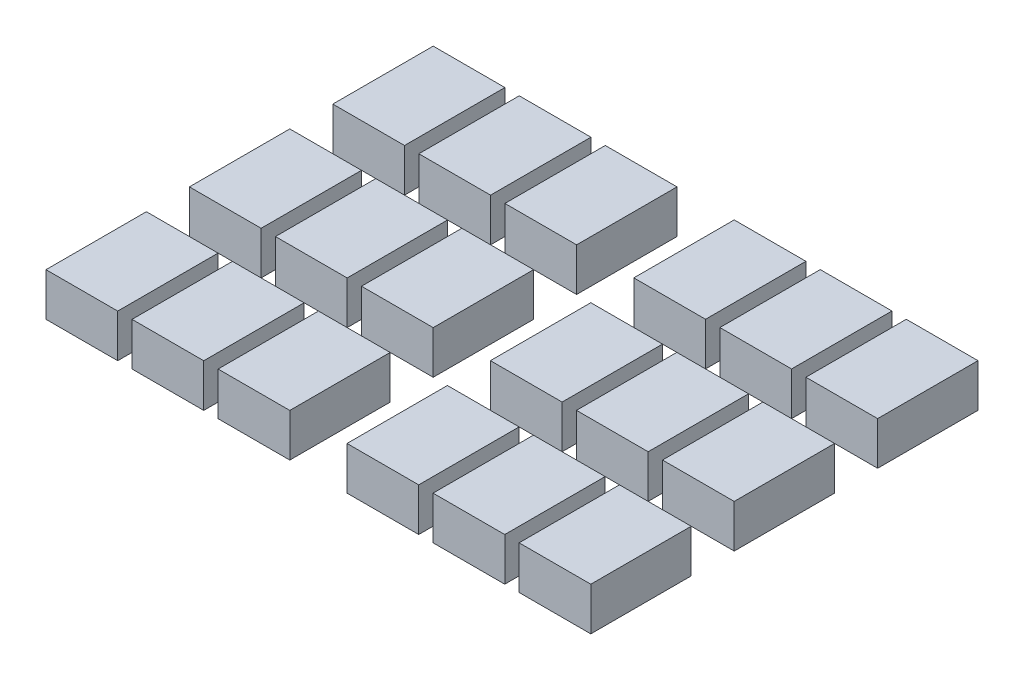
SolidWorks part; units mm, degrees
ref_plane "Front Plane" through (0, 0, 0) normal (0, 0, 1) x (1, 0, 0)
ref_plane "Top Plane" through (0, 0, 0) normal (0, 1, 0) x (1, 0, 0)
ref_plane "Right Plane" through (0, 0, 0) normal (1, 0, 0) x (0, 0, -1)
sketch "First Class Seat" plane through (0, 0, 0) normal (0, 1, 0) x (1, 0, 0)
  line L0 (-1320.292, 13858.7872) -> (-812.292, 13858.7872)
  line L1 (-1993.392, 18288) -> (1993.392, 18288) construction
  line L2 (-1993.392, 18288) -> (-1993.392, -18288) construction
  line L3 (-1993.392, -18288) -> (1993.392, -18288) construction
  line L4 (1993.392, 18288) -> (1993.392, -18288) construction
  line L5 (-1993.392, 18288) -> (1993.392, -18288) construction
  line L6 (-1993.392, -18288) -> (1993.392, 18288) construction
  line L11 (-1929.892, 13858.7872) -> (-1421.892, 13858.7872)
  line L12 (-1929.892, 13858.7872) -> (-1929.892, 13147.5872)
  line L13 (-1929.892, 13147.5872) -> (-1421.892, 13147.5872)
  line L14 (-1421.892, 13858.7872) -> (-1421.892, 13147.5872)
  line L15 (-1320.292, 13858.7872) -> (-1320.292, 13147.5872)
  line L16 (-1320.292, 13147.5872) -> (-812.292, 13147.5872)
  line L17 (-812.292, 13858.7872) -> (-812.292, 13147.5872)
  line L18 (-710.692, 13858.7872) -> (-202.692, 13858.7872)
  line L19 (-710.692, 13858.7872) -> (-710.692, 13147.5872)
  line L20 (-710.692, 13147.5872) -> (-202.692, 13147.5872)
  line L21 (-202.692, 13858.7872) -> (-202.692, 13147.5872)
  line L22 (-1320.292, 14874.7872) -> (-812.292, 14874.7872)
  line L23 (-1320.292, 14874.7872) -> (-1320.292, 14163.5872)
  line L24 (-1320.292, 14163.5872) -> (-812.292, 14163.5872)
  line L25 (-812.292, 14874.7872) -> (-812.292, 14163.5872)
  line L26 (-710.692, 14874.7872) -> (-202.692, 14874.7872)
  line L27 (-710.692, 14874.7872) -> (-710.692, 14163.5872)
  line L28 (-710.692, 14163.5872) -> (-202.692, 14163.5872)
  line L29 (-202.692, 14874.7872) -> (-202.692, 14163.5872)
  line L30 (-1320.292, 15890.7872) -> (-812.292, 15890.7872)
  line L31 (-1320.292, 15890.7872) -> (-1320.292, 15179.5872)
  line L32 (-1320.292, 15179.5872) -> (-812.292, 15179.5872)
  line L33 (-812.292, 15890.7872) -> (-812.292, 15179.5872)
  line L34 (-710.692, 15890.7872) -> (-202.692, 15890.7872)
  line L35 (-710.692, 15890.7872) -> (-710.692, 15179.5872)
  line L36 (-710.692, 15179.5872) -> (-202.692, 15179.5872)
  line L37 (-202.692, 15890.7872) -> (-202.692, 15179.5872)
  line L38 (-1929.892, 14874.7872) -> (-1421.892, 14874.7872)
  line L39 (-1929.892, 14874.7872) -> (-1929.892, 14163.5872)
  line L40 (-1929.892, 14163.5872) -> (-1421.892, 14163.5872)
  line L41 (-1421.892, 14874.7872) -> (-1421.892, 14163.5872)
  line L42 (-1929.892, 15890.7872) -> (-1421.892, 15890.7872)
  line L43 (-1929.892, 15890.7872) -> (-1929.892, 15179.5872)
  line L44 (-1929.892, 15179.5872) -> (-1421.892, 15179.5872)
  line L45 (-1421.892, 15890.7872) -> (-1421.892, 15179.5872)
  line L46 (0, 18288) -> (0, -18288) construction
  line L47 (1421.892, 15890.7872) -> (1421.892, 15179.5872)
  line L48 (1929.892, 15179.5872) -> (1421.892, 15179.5872)
  line L49 (1929.892, 15890.7872) -> (1929.892, 15179.5872)
  line L50 (1929.892, 15890.7872) -> (1421.892, 15890.7872)
  line L51 (1421.892, 14874.7872) -> (1421.892, 14163.5872)
  line L52 (1929.892, 14163.5872) -> (1421.892, 14163.5872)
  line L53 (1929.892, 14874.7872) -> (1929.892, 14163.5872)
  line L54 (1929.892, 14874.7872) -> (1421.892, 14874.7872)
  line L55 (202.692, 15890.7872) -> (202.692, 15179.5872)
  line L56 (710.692, 15179.5872) -> (202.692, 15179.5872)
  line L57 (710.692, 15890.7872) -> (710.692, 15179.5872)
  line L58 (710.692, 15890.7872) -> (202.692, 15890.7872)
  line L59 (812.292, 15890.7872) -> (812.292, 15179.5872)
  line L60 (1320.292, 15179.5872) -> (812.292, 15179.5872)
  line L61 (1320.292, 15890.7872) -> (1320.292, 15179.5872)
  line L62 (1320.292, 15890.7872) -> (812.292, 15890.7872)
  line L63 (202.692, 14874.7872) -> (202.692, 14163.5872)
  line L64 (710.692, 14163.5872) -> (202.692, 14163.5872)
  line L65 (710.692, 14874.7872) -> (710.692, 14163.5872)
  line L66 (710.692, 14874.7872) -> (202.692, 14874.7872)
  line L67 (812.292, 14874.7872) -> (812.292, 14163.5872)
  line L68 (1320.292, 14163.5872) -> (812.292, 14163.5872)
  line L69 (1320.292, 14874.7872) -> (1320.292, 14163.5872)
  line L70 (1320.292, 14874.7872) -> (812.292, 14874.7872)
  line L71 (202.692, 13858.7872) -> (202.692, 13147.5872)
  line L72 (710.692, 13147.5872) -> (202.692, 13147.5872)
  line L73 (710.692, 13858.7872) -> (710.692, 13147.5872)
  line L74 (710.692, 13858.7872) -> (202.692, 13858.7872)
  line L75 (812.292, 13858.7872) -> (812.292, 13147.5872)
  line L76 (1320.292, 13147.5872) -> (812.292, 13147.5872)
  line L77 (1320.292, 13858.7872) -> (1320.292, 13147.5872)
  line L78 (1421.892, 13858.7872) -> (1421.892, 13147.5872)
  line L79 (1929.892, 13147.5872) -> (1421.892, 13147.5872)
  line L80 (1929.892, 13858.7872) -> (1929.892, 13147.5872)
  line L81 (1929.892, 13858.7872) -> (1421.892, 13858.7872)
  line L82 (1320.292, 13858.7872) -> (812.292, 13858.7872)
  point P0 (0, 0)
  point P10 (-1874.4664, 14436.0926)
  point P45 (0, 0)
  point P46 (0, 0)
  point P47 (-1893.0211, 14361.6296)
  point P84 (-1942.592, 14425.8266)
  point P85 (-1929.892, 12907.0433)
  point P86 (-1929.892, 13226.5881)
  point P87 (-1929.892, 13139.258)
  point P88 (-1929.892, 16238.2689)
  point P89 (0, 0)
  point P90 (-1993.392, 11778.9178)
  point P91 (0, 0)
  point P92 (-1929.892, 12245.8872)
  dimension "D1" = 36576
  dimension "D2" = 3986.784
  dimension "D3" = 508
  dimension "D4" = 711.2
  dimension "D7" = 1016
  dimension "D8" = 101.6
  dimension "D9" = 63.5
  dimension "D10" = 405.384
  dimension "D5" = 3
  dimension "D6" = 3
extrude "First Class Seat-" add sketch "First Class Seat" along normal blind 304.8
sketch "First Class LAV" plane through (0, 0, 0) normal (0, 1, 0) x (1, 0, 0)
  line L1 (-1993.392, 18288) -> (-977.392, 18288)
  line L2 (-1993.392, 18288) -> (-1993.392, 17322.8)
  line L3 (-1993.392, 17322.8) -> (-977.392, 17322.8)
  line L4 (-977.392, 18288) -> (-977.392, 17322.8)
  line L5 (-1993.392, 18288) -> (-1993.392, -18288) construction
  line L6 (0, 0) -> (0, 585.7806) construction
  line L9 (-1993.392, 18288) -> (1993.392, -18288) construction
  line L10 (0, 18288) -> (0, -18288) construction
  line L11 (977.392, 18288) -> (977.392, 17322.8)
  line L12 (1993.392, 17322.8) -> (977.392, 17322.8)
  line L13 (1993.392, 18288) -> (1993.392, 17322.8)
  line L14 (1993.392, 18288) -> (977.392, 18288)
  point P16 (-1972.7451, 17206.2188)
  point P17 (-1993.392, 16421.1)
  dimension "D1" = 1016
  dimension "D2" = 965.2
sketch "First Class Galley" plane through (0, 0, 0) normal (0, 1, 0) x (1, 0, 0)
  line L0 (-1993.392, 18288) -> (-1993.392, -18288) construction
  line L1 (-1993.392, 16508.5663) -> (-1028.192, 16508.5663)
  line L2 (-1993.392, 16508.5663) -> (-1993.392, 16127.5663)
  line L3 (-1993.392, 16127.5663) -> (-1028.192, 16127.5663)
  line L4 (-1028.192, 16508.5663) -> (-1028.192, 16127.5663)
  line L5 (-1993.392, 16892.6143) -> (-1028.192, 16892.6143)
  line L6 (-1993.392, 16892.6143) -> (-1993.392, 16511.6143)
  line L7 (-1993.392, 16511.6143) -> (-1028.192, 16511.6143)
  line L8 (-1028.192, 16892.6143) -> (-1028.192, 16511.6143)
  line L9 (-1993.392, 17276.6623) -> (-1028.192, 17276.6623)
  line L10 (-1993.392, 17276.6623) -> (-1993.392, 16895.6623)
  line L11 (-1993.392, 16895.6623) -> (-1028.192, 16895.6623)
  line L12 (-1028.192, 17276.6623) -> (-1028.192, 16895.6623)
  line L13 (0, -20116.8) -> (0, 20116.8) construction
  line L14 (1028.192, 17276.6623) -> (1028.192, 16895.6623)
  line L15 (1993.392, 16895.6623) -> (1028.192, 16895.6623)
  line L16 (1993.392, 17276.6623) -> (1993.392, 16895.6623)
  line L17 (1993.392, 17276.6623) -> (1028.192, 17276.6623)
  line L18 (1028.192, 16892.6143) -> (1028.192, 16511.6143)
  line L19 (1993.392, 16511.6143) -> (1028.192, 16511.6143)
  line L20 (1993.392, 16892.6143) -> (1993.392, 16511.6143)
  line L21 (1993.392, 16892.6143) -> (1028.192, 16892.6143)
  line L22 (1028.192, 16508.5663) -> (1028.192, 16127.5663)
  line L23 (1993.392, 16127.5663) -> (1028.192, 16127.5663)
  line L24 (1993.392, 16508.5663) -> (1993.392, 16127.5663)
  line L25 (1993.392, 16508.5663) -> (1028.192, 16508.5663)
  point P4 (-1993.392, 14804.2428)
  point P5 (-1993.392, 15167.2745)
  point P30 (-1993.392, 16071.3168)
  dimension "D1" = 381
  dimension "D2" = 965.2
  dimension "D4" = 3.048
  dimension "D3" = 3
sketch "First Class Coat Room" plane through (0, 0, 0) normal (0, 1, 0) x (1, 0, 0)
  line L0 (-1993.392, 18288) -> (-1993.392, -18288) construction
  line L1 (-1993.392, 13011.8143) -> (1993.392, 13011.8143)
  line L2 (-1993.392, 13011.8143) -> (-1993.392, 12326.0143)
  line L3 (-1993.392, 12326.0143) -> (1993.392, 12326.0143)
  line L4 (1993.392, 13011.8143) -> (1993.392, 12326.0143)
  line L5 (1993.392, 18288) -> (1993.392, -18288) construction
  point P8 (-1993.392, 11424.9048)
  point P9 (-1993.392, 13011.8143)
  dimension "D1" = 685.8
sketch "EM Exits" plane through (0, 0, 0) normal (0, 1, 0) x (1, 0, 0)
  line L0 (-1993.392, 18288) -> (-1993.392, -18288) construction
  line L1 (-1993.392, 12326.0143) -> (-1940.4514, 12326.0143)
  line L2 (-1993.392, 12326.0143) -> (-1993.392, 11259.2143)
  line L3 (-1993.392, 11259.2143) -> (-1940.4514, 11259.2143)
  line L4 (-1940.4514, 12326.0143) -> (-1940.4514, 11259.2143)
  line L5 (-1993.392, 12326.0143) -> (1993.392, 12326.0143) construction
  line L6 (0, -20116.8) -> (0, 20116.8) construction
  line L7 (-1993.392, -7028.7857) -> (-1940.4514, -7028.7857)
  line L8 (-1993.392, -7028.7857) -> (-1993.392, -8095.5857)
  line L9 (-1993.392, -8095.5857) -> (-1940.4514, -8095.5857)
  line L10 (-1940.4514, -7028.7857) -> (-1940.4514, -8095.5857)
  line L11 (1940.4514, -7028.7857) -> (1940.4514, -8095.5857)
  line L12 (1993.392, -8095.5857) -> (1940.4514, -8095.5857)
  line L13 (1993.392, -7028.7857) -> (1993.392, -8095.5857)
  line L14 (1993.392, -7028.7857) -> (1940.4514, -7028.7857)
  line L15 (1940.4514, 12326.0143) -> (1940.4514, 11259.2143)
  line L16 (1993.392, 11259.2143) -> (1940.4514, 11259.2143)
  line L17 (1993.392, 12326.0143) -> (1993.392, 11259.2143)
  line L18 (1993.392, 12326.0143) -> (1940.4514, 12326.0143)
  line L19 (-1940.4514, 11259.2143) -> (1940.4514, 11259.2143) construction
  line L20 (-1940.4514, -7028.7857) -> (1940.4514, -7028.7857) construction
  line L21 (1940.4514, -8095.5857) -> (-1940.4514, -8095.5857) construction
  line L22 (-1940.4514, -7562.1857) -> (1940.4514, -7562.1857) construction
  line L23 (-1940.4514, 11792.6143) -> (1940.4514, 11792.6143) construction
  line L24 (1940.4514, 12326.0143) -> (-1940.4514, 12326.0143) construction
  point P26 (-1993.392, 12326.0143)
  dimension "D1" = 1066.8
  dimension "D2" = 0
  dimension "D3" = 1066.8
  dimension "D4" = 18288
sketch "Econ LAV" plane through (0, 0, 0) normal (0, 1, 0) x (1, 0, 0)
  line L0 (-1993.392, 11259.2143) -> (-977.392, 11259.2143)
  line L1 (-1993.392, 11259.2143) -> (-1993.392, 10294.0143)
  line L2 (-1993.392, 10294.0143) -> (-977.392, 10294.0143)
  line L3 (-977.392, 11259.2143) -> (-977.392, 10294.0143)
  line L8 (-1993.392, -17322.8) -> (-977.392, -17322.8)
  line L9 (-1993.392, -17322.8) -> (-1993.392, -18288)
  line L10 (-1993.392, -18288) -> (-977.392, -18288)
  line L11 (-977.392, -17322.8) -> (-977.392, -18288)
  line L12 (0, -20116.8) -> (0, 20116.8) construction
  line L13 (977.392, -17322.8) -> (977.392, -18288)
  line L14 (1993.392, -18288) -> (977.392, -18288)
  line L15 (1993.392, -17322.8) -> (1993.392, -18288)
  line L16 (1993.392, -17322.8) -> (977.392, -17322.8)
  line L17 (977.392, 11259.2143) -> (977.392, 10294.0143)
  line L18 (1993.392, 10294.0143) -> (977.392, 10294.0143)
  line L19 (1993.392, 11259.2143) -> (1993.392, 10294.0143)
  line L20 (1993.392, 11259.2143) -> (977.392, 11259.2143)
  point P4 (-1748.2194, 9202.9834)
  point P5 (-1772.2723, 9247.487)
  point P6 (-1993.392, 10358.1048)
  point P8 (-1786.9164, 7219.1182)
  point P13 (-1993.392, -17386.3)
  dimension "D1" = 1016
  dimension "D2" = 965.2
  dimension "D3" = 1016
  dimension "D4" = 965.2
sketch "Econ Seat" plane through (0, 0, 0) normal (0, 1, 0) x (1, 0, 0)
  line L1 (-1929.892, -16523.2246) -> (-1472.692, -16523.2246)
  line L2 (-1929.892, -16523.2246) -> (-1929.892, -17158.2246)
  line L3 (-1929.892, -17158.2246) -> (-1472.692, -17158.2246)
  line L4 (-1472.692, -16523.2246) -> (-1472.692, -17158.2246)
  line L36 (-1421.892, -16523.2246) -> (-964.692, -16523.2246)
  line L37 (-1421.892, -16523.2246) -> (-1421.892, -17158.2246)
  line L38 (-1421.892, -17158.2246) -> (-964.692, -17158.2246)
  line L39 (-964.692, -16523.2246) -> (-964.692, -17158.2246)
  line L40 (-913.892, -16523.2246) -> (-456.692, -16523.2246)
  line L41 (-913.892, -16523.2246) -> (-913.892, -17158.2246)
  line L42 (-913.892, -17158.2246) -> (-456.692, -17158.2246)
  line L43 (-456.692, -16523.2246) -> (-456.692, -17158.2246)
  line L44 (-1421.892, -15710.4246) -> (-964.692, -15710.4246)
  line L45 (-1421.892, -15710.4246) -> (-1421.892, -16345.4246)
  line L46 (-1421.892, -16345.4246) -> (-964.692, -16345.4246)
  line L47 (-964.692, -15710.4246) -> (-964.692, -16345.4246)
  line L48 (-913.892, -15710.4246) -> (-456.692, -15710.4246)
  line L49 (-913.892, -15710.4246) -> (-913.892, -16345.4246)
  line L50 (-913.892, -16345.4246) -> (-456.692, -16345.4246)
  line L51 (-456.692, -15710.4246) -> (-456.692, -16345.4246)
  line L52 (-1421.892, -14897.6246) -> (-964.692, -14897.6246)
  line L53 (-1421.892, -14897.6246) -> (-1421.892, -15532.6246)
  line L54 (-1421.892, -15532.6246) -> (-964.692, -15532.6246)
  line L55 (-964.692, -14897.6246) -> (-964.692, -15532.6246)
  line L56 (-913.892, -14897.6246) -> (-456.692, -14897.6246)
  line L57 (-913.892, -14897.6246) -> (-913.892, -15532.6246)
  line L58 (-913.892, -15532.6246) -> (-456.692, -15532.6246)
  line L59 (-456.692, -14897.6246) -> (-456.692, -15532.6246)
  line L60 (-1929.892, -15710.4246) -> (-1472.692, -15710.4246)
  line L61 (-1929.892, -15710.4246) -> (-1929.892, -16345.4246)
  line L62 (-1929.892, -16345.4246) -> (-1472.692, -16345.4246)
  line L63 (-1472.692, -15710.4246) -> (-1472.692, -16345.4246)
  line L64 (-1929.892, -14897.6246) -> (-1472.692, -14897.6246)
  line L65 (-1929.892, -14897.6246) -> (-1929.892, -15532.6246)
  line L66 (-1929.892, -15532.6246) -> (-1472.692, -15532.6246)
  line L67 (-1472.692, -14897.6246) -> (-1472.692, -15532.6246)
  line L68 (-1993.392, 18288) -> (-1993.392, -18288) construction
  line L69 (-1929.892, -9208.0246) -> (-1472.692, -9208.0246)
  line L106 (-1929.892, -14084.8246) -> (-1472.692, -14084.8246)
  line L107 (-1929.892, -14084.8246) -> (-1929.892, -14719.8246)
  line L108 (-1929.892, -14719.8246) -> (-1472.692, -14719.8246)
  line L109 (-1472.692, -14084.8246) -> (-1472.692, -14719.8246)
  line L110 (-1421.892, -14084.8246) -> (-964.692, -14084.8246)
  line L111 (-1421.892, -14084.8246) -> (-1421.892, -14719.8246)
  line L112 (-1421.892, -14719.8246) -> (-964.692, -14719.8246)
  line L113 (-964.692, -14084.8246) -> (-964.692, -14719.8246)
  line L114 (-913.892, -14084.8246) -> (-456.692, -14084.8246)
  line L115 (-913.892, -14084.8246) -> (-913.892, -14719.8246)
  line L116 (-913.892, -14719.8246) -> (-456.692, -14719.8246)
  line L117 (-456.692, -14084.8246) -> (-456.692, -14719.8246)
  line L118 (-1929.892, -13272.0246) -> (-1472.692, -13272.0246)
  line L119 (-1929.892, -13272.0246) -> (-1929.892, -13907.0246)
  line L120 (-1929.892, -13907.0246) -> (-1472.692, -13907.0246)
  line L121 (-1472.692, -13272.0246) -> (-1472.692, -13907.0246)
  line L122 (-1421.892, -13272.0246) -> (-964.692, -13272.0246)
  line L123 (-1421.892, -13272.0246) -> (-1421.892, -13907.0246)
  line L124 (-1421.892, -13907.0246) -> (-964.692, -13907.0246)
  line L125 (-964.692, -13272.0246) -> (-964.692, -13907.0246)
  line L126 (-913.892, -13272.0246) -> (-456.692, -13272.0246)
  line L127 (-913.892, -13272.0246) -> (-913.892, -13907.0246)
  line L128 (-913.892, -13907.0246) -> (-456.692, -13907.0246)
  line L129 (-456.692, -13272.0246) -> (-456.692, -13907.0246)
  line L130 (-1929.892, -12459.2246) -> (-1472.692, -12459.2246)
  line L131 (-1929.892, -12459.2246) -> (-1929.892, -13094.2246)
  line L132 (-1929.892, -13094.2246) -> (-1472.692, -13094.2246)
  line L133 (-1472.692, -12459.2246) -> (-1472.692, -13094.2246)
  line L134 (-1421.892, -12459.2246) -> (-964.692, -12459.2246)
  line L135 (-1421.892, -12459.2246) -> (-1421.892, -13094.2246)
  line L136 (-1421.892, -13094.2246) -> (-964.692, -13094.2246)
  line L137 (-964.692, -12459.2246) -> (-964.692, -13094.2246)
  line L138 (-913.892, -12459.2246) -> (-456.692, -12459.2246)
  line L139 (-913.892, -12459.2246) -> (-913.892, -13094.2246)
  line L140 (-913.892, -13094.2246) -> (-456.692, -13094.2246)
  line L141 (-456.692, -12459.2246) -> (-456.692, -13094.2246)
  line L142 (-1929.892, -11646.4246) -> (-1472.692, -11646.4246)
  line L143 (-1929.892, -11646.4246) -> (-1929.892, -12281.4246)
  line L144 (-1929.892, -12281.4246) -> (-1472.692, -12281.4246)
  line L145 (-1472.692, -11646.4246) -> (-1472.692, -12281.4246)
  line L146 (-1421.892, -11646.4246) -> (-964.692, -11646.4246)
  line L147 (-1421.892, -11646.4246) -> (-1421.892, -12281.4246)
  line L148 (-1421.892, -12281.4246) -> (-964.692, -12281.4246)
  line L149 (-964.692, -11646.4246) -> (-964.692, -12281.4246)
  line L150 (-913.892, -11646.4246) -> (-456.692, -11646.4246)
  line L151 (-913.892, -11646.4246) -> (-913.892, -12281.4246)
  line L152 (-913.892, -12281.4246) -> (-456.692, -12281.4246)
  line L153 (-456.692, -11646.4246) -> (-456.692, -12281.4246)
  line L154 (-1929.892, -10833.6246) -> (-1472.692, -10833.6246)
  line L155 (-1929.892, -10833.6246) -> (-1929.892, -11468.6246)
  line L156 (-1929.892, -11468.6246) -> (-1472.692, -11468.6246)
  line L157 (-1472.692, -10833.6246) -> (-1472.692, -11468.6246)
  line L158 (-1421.892, -10833.6246) -> (-964.692, -10833.6246)
  line L159 (-1421.892, -10833.6246) -> (-1421.892, -11468.6246)
  line L160 (-1421.892, -11468.6246) -> (-964.692, -11468.6246)
  line L161 (-964.692, -10833.6246) -> (-964.692, -11468.6246)
  line L162 (-913.892, -10833.6246) -> (-456.692, -10833.6246)
  line L163 (-913.892, -10833.6246) -> (-913.892, -11468.6246)
  line L164 (-913.892, -11468.6246) -> (-456.692, -11468.6246)
  line L165 (-456.692, -10833.6246) -> (-456.692, -11468.6246)
  line L166 (-1929.892, -10020.8246) -> (-1472.692, -10020.8246)
  line L167 (-1929.892, -10020.8246) -> (-1929.892, -10655.8246)
  line L168 (-1929.892, -10655.8246) -> (-1472.692, -10655.8246)
  line L169 (-1472.692, -10020.8246) -> (-1472.692, -10655.8246)
  line L170 (-1421.892, -10020.8246) -> (-964.692, -10020.8246)
  line L171 (-1421.892, -10020.8246) -> (-1421.892, -10655.8246)
  line L172 (-1421.892, -10655.8246) -> (-964.692, -10655.8246)
  line L173 (-964.692, -10020.8246) -> (-964.692, -10655.8246)
  line L174 (-913.892, -10020.8246) -> (-456.692, -10020.8246)
  line L175 (-913.892, -10020.8246) -> (-913.892, -10655.8246)
  line L176 (-913.892, -10655.8246) -> (-456.692, -10655.8246)
  line L177 (-456.692, -10020.8246) -> (-456.692, -10655.8246)
  line L299 (-1929.892, -6181.3562) -> (-1472.692, -6181.3562)
  line L300 (-1929.892, -6181.3562) -> (-1929.892, -6816.3562)
  line L301 (-1929.892, -6816.3562) -> (-1472.692, -6816.3562)
  line L302 (-1472.692, -6181.3562) -> (-1472.692, -6816.3562)
  line L303 (-1422.9719, -6181.3562) -> (-965.7719, -6181.3562)
  line L304 (-1422.9719, -6181.3562) -> (-1422.9719, -6816.3562)
  line L305 (-1422.9719, -6816.3562) -> (-965.7719, -6816.3562)
  line L306 (-965.7719, -6181.3562) -> (-965.7719, -6816.3562)
  line L307 (-916.0518, -6181.3562) -> (-458.8518, -6181.3562)
  line L308 (-916.0518, -6181.3562) -> (-916.0518, -6816.3562)
  line L309 (-916.0518, -6816.3562) -> (-458.8518, -6816.3562)
  line L310 (-458.8518, -6181.3562) -> (-458.8518, -6816.3562)
  line L311 (-1422.9719, -5368.5562) -> (-965.7719, -5368.5562)
  line L312 (-1422.9719, -5368.5562) -> (-1422.9719, -6003.5562)
  line L313 (-1422.9719, -6003.5562) -> (-965.7719, -6003.5562)
  line L314 (-965.7719, -5368.5562) -> (-965.7719, -6003.5562)
  line L315 (-916.0518, -5368.5562) -> (-458.8518, -5368.5562)
  line L316 (-916.0518, -5368.5562) -> (-916.0518, -6003.5562)
  line L317 (-916.0518, -6003.5562) -> (-458.8518, -6003.5562)
  line L318 (-458.8518, -5368.5562) -> (-458.8518, -6003.5562)
  line L319 (-1422.9719, -4555.7562) -> (-965.7719, -4555.7562)
  line L320 (-1422.9719, -4555.7562) -> (-1422.9719, -5190.7562)
  line L321 (-1422.9719, -5190.7562) -> (-965.7719, -5190.7562)
  line L322 (-965.7719, -4555.7562) -> (-965.7719, -5190.7562)
  line L323 (-916.0518, -4555.7562) -> (-458.8518, -4555.7562)
  line L324 (-916.0518, -4555.7562) -> (-916.0518, -5190.7562)
  line L325 (-916.0518, -5190.7562) -> (-458.8518, -5190.7562)
  line L326 (-458.8518, -4555.7562) -> (-458.8518, -5190.7562)
  line L327 (-1422.9719, -3742.9562) -> (-965.7719, -3742.9562)
  line L328 (-1422.9719, -3742.9562) -> (-1422.9719, -4377.9562)
  line L329 (-1422.9719, -4377.9562) -> (-965.7719, -4377.9562)
  line L330 (-965.7719, -3742.9562) -> (-965.7719, -4377.9562)
  line L331 (-916.0518, -3742.9562) -> (-458.8518, -3742.9562)
  line L332 (-916.0518, -3742.9562) -> (-916.0518, -4377.9562)
  line L333 (-916.0518, -4377.9562) -> (-458.8518, -4377.9562)
  line L334 (-458.8518, -3742.9562) -> (-458.8518, -4377.9562)
  line L335 (-1422.9719, -2930.1562) -> (-965.7719, -2930.1562)
  line L336 (-1422.9719, -2930.1562) -> (-1422.9719, -3565.1562)
  line L337 (-1422.9719, -3565.1562) -> (-965.7719, -3565.1562)
  line L338 (-965.7719, -2930.1562) -> (-965.7719, -3565.1562)
  line L339 (-916.0518, -2930.1562) -> (-458.8518, -2930.1562)
  line L340 (-916.0518, -2930.1562) -> (-916.0518, -3565.1562)
  line L341 (-916.0518, -3565.1562) -> (-458.8518, -3565.1562)
  line L342 (-458.8518, -2930.1562) -> (-458.8518, -3565.1562)
  line L343 (-1422.9719, -2117.3562) -> (-965.7719, -2117.3562)
  line L344 (-1422.9719, -2117.3562) -> (-1422.9719, -2752.3562)
  line L345 (-1422.9719, -2752.3562) -> (-965.7719, -2752.3562)
  line L346 (-965.7719, -2117.3562) -> (-965.7719, -2752.3562)
  line L347 (-916.0518, -2117.3562) -> (-458.8518, -2117.3562)
  line L348 (-916.0518, -2117.3562) -> (-916.0518, -2752.3562)
  line L349 (-916.0518, -2752.3562) -> (-458.8518, -2752.3562)
  line L350 (-458.8518, -2117.3562) -> (-458.8518, -2752.3562)
  line L351 (-1422.9719, -1304.5562) -> (-965.7719, -1304.5562)
  line L352 (-1422.9719, -1304.5562) -> (-1422.9719, -1939.5562)
  line L353 (-1422.9719, -1939.5562) -> (-965.7719, -1939.5562)
  line L354 (-965.7719, -1304.5562) -> (-965.7719, -1939.5562)
  line L355 (-916.0518, -1304.5562) -> (-458.8518, -1304.5562)
  line L356 (-916.0518, -1304.5562) -> (-916.0518, -1939.5562)
  line L357 (-916.0518, -1939.5562) -> (-458.8518, -1939.5562)
  line L358 (-458.8518, -1304.5562) -> (-458.8518, -1939.5562)
  line L359 (-1422.9719, -491.7562) -> (-965.7719, -491.7562)
  line L360 (-1422.9719, -491.7562) -> (-1422.9719, -1126.7562)
  line L361 (-1422.9719, -1126.7562) -> (-965.7719, -1126.7562)
  line L362 (-965.7719, -491.7562) -> (-965.7719, -1126.7562)
  line L363 (-916.0518, -491.7562) -> (-458.8518, -491.7562)
  line L364 (-916.0518, -491.7562) -> (-916.0518, -1126.7562)
  line L365 (-916.0518, -1126.7562) -> (-458.8518, -1126.7562)
  line L366 (-458.8518, -491.7562) -> (-458.8518, -1126.7562)
  line L367 (-1422.9719, 321.0438) -> (-965.7719, 321.0438)
  line L368 (-1422.9719, 321.0438) -> (-1422.9719, -313.9562)
  line L369 (-1422.9719, -313.9562) -> (-965.7719, -313.9562)
  line L370 (-965.7719, 321.0438) -> (-965.7719, -313.9562)
  line L371 (-916.0518, 321.0438) -> (-458.8518, 321.0438)
  line L372 (-916.0518, 321.0438) -> (-916.0518, -313.9562)
  line L373 (-916.0518, -313.9562) -> (-458.8518, -313.9562)
  line L374 (-458.8518, 321.0438) -> (-458.8518, -313.9562)
  line L375 (-1422.9719, 1133.8438) -> (-965.7719, 1133.8438)
  line L376 (-1422.9719, 1133.8438) -> (-1422.9719, 498.8438)
  line L377 (-1422.9719, 498.8438) -> (-965.7719, 498.8438)
  line L378 (-965.7719, 1133.8438) -> (-965.7719, 498.8438)
  line L379 (-916.0518, 1133.8438) -> (-458.8518, 1133.8438)
  line L380 (-916.0518, 1133.8438) -> (-916.0518, 498.8438)
  line L381 (-916.0518, 498.8438) -> (-458.8518, 498.8438)
  line L382 (-458.8518, 1133.8438) -> (-458.8518, 498.8438)
  line L383 (-1422.9719, 1946.6438) -> (-965.7719, 1946.6438)
  line L384 (-1422.9719, 1946.6438) -> (-1422.9719, 1311.6438)
  line L385 (-1422.9719, 1311.6438) -> (-965.7719, 1311.6438)
  line L386 (-965.7719, 1946.6438) -> (-965.7719, 1311.6438)
  line L387 (-916.0518, 1946.6438) -> (-458.8518, 1946.6438)
  line L388 (-916.0518, 1946.6438) -> (-916.0518, 1311.6438)
  line L389 (-916.0518, 1311.6438) -> (-458.8518, 1311.6438)
  line L390 (-458.8518, 1946.6438) -> (-458.8518, 1311.6438)
  line L391 (-1422.9719, 2759.4438) -> (-965.7719, 2759.4438)
  line L392 (-1422.9719, 2759.4438) -> (-1422.9719, 2124.4438)
  line L393 (-1422.9719, 2124.4438) -> (-965.7719, 2124.4438)
  line L394 (-965.7719, 2759.4438) -> (-965.7719, 2124.4438)
  line L395 (-916.0518, 2759.4438) -> (-458.8518, 2759.4438)
  line L396 (-916.0518, 2759.4438) -> (-916.0518, 2124.4438)
  line L397 (-916.0518, 2124.4438) -> (-458.8518, 2124.4438)
  line L398 (-458.8518, 2759.4438) -> (-458.8518, 2124.4438)
  line L399 (-1422.9719, 3572.2438) -> (-965.7719, 3572.2438)
  line L400 (-1422.9719, 3572.2438) -> (-1422.9719, 2937.2438)
  line L401 (-1422.9719, 2937.2438) -> (-965.7719, 2937.2438)
  line L402 (-965.7719, 3572.2438) -> (-965.7719, 2937.2438)
  line L403 (-916.0518, 3572.2438) -> (-458.8518, 3572.2438)
  line L404 (-916.0518, 3572.2438) -> (-916.0518, 2937.2438)
  line L405 (-916.0518, 2937.2438) -> (-458.8518, 2937.2438)
  line L406 (-458.8518, 3572.2438) -> (-458.8518, 2937.2438)
  line L407 (-1422.9719, 4385.0438) -> (-965.7719, 4385.0438)
  line L408 (-1422.9719, 4385.0438) -> (-1422.9719, 3750.0438)
  line L409 (-1422.9719, 3750.0438) -> (-965.7719, 3750.0438)
  line L410 (-965.7719, 4385.0438) -> (-965.7719, 3750.0438)
  line L411 (-916.0518, 4385.0438) -> (-458.8518, 4385.0438)
  line L412 (-916.0518, 4385.0438) -> (-916.0518, 3750.0438)
  line L413 (-916.0518, 3750.0438) -> (-458.8518, 3750.0438)
  line L414 (-458.8518, 4385.0438) -> (-458.8518, 3750.0438)
  line L415 (-1422.9719, 5197.8438) -> (-965.7719, 5197.8438)
  line L416 (-1422.9719, 5197.8438) -> (-1422.9719, 4562.8438)
  line L417 (-1422.9719, 4562.8438) -> (-965.7719, 4562.8438)
  line L418 (-965.7719, 5197.8438) -> (-965.7719, 4562.8438)
  line L419 (-916.0518, 5197.8438) -> (-458.8518, 5197.8438)
  line L420 (-916.0518, 5197.8438) -> (-916.0518, 4562.8438)
  line L421 (-916.0518, 4562.8438) -> (-458.8518, 4562.8438)
  line L422 (-458.8518, 5197.8438) -> (-458.8518, 4562.8438)
  line L423 (-1422.9719, 6010.6438) -> (-965.7719, 6010.6438)
  line L424 (-1422.9719, 6010.6438) -> (-1422.9719, 5375.6438)
  line L425 (-1422.9719, 5375.6438) -> (-965.7719, 5375.6438)
  line L426 (-965.7719, 6010.6438) -> (-965.7719, 5375.6438)
  line L427 (-916.0518, 6010.6438) -> (-458.8518, 6010.6438)
  line L428 (-916.0518, 6010.6438) -> (-916.0518, 5375.6438)
  line L429 (-916.0518, 5375.6438) -> (-458.8518, 5375.6438)
  line L430 (-458.8518, 6010.6438) -> (-458.8518, 5375.6438)
  line L431 (-1422.9719, 6823.4438) -> (-965.7719, 6823.4438)
  line L432 (-1422.9719, 6823.4438) -> (-1422.9719, 6188.4438)
  line L433 (-1422.9719, 6188.4438) -> (-965.7719, 6188.4438)
  line L434 (-965.7719, 6823.4438) -> (-965.7719, 6188.4438)
  line L435 (-916.0518, 6823.4438) -> (-458.8518, 6823.4438)
  line L436 (-916.0518, 6823.4438) -> (-916.0518, 6188.4438)
  line L437 (-916.0518, 6188.4438) -> (-458.8518, 6188.4438)
  line L438 (-458.8518, 6823.4438) -> (-458.8518, 6188.4438)
  line L439 (-1422.9719, 7636.2438) -> (-965.7719, 7636.2438)
  line L440 (-1422.9719, 7636.2438) -> (-1422.9719, 7001.2438)
  line L441 (-1422.9719, 7001.2438) -> (-965.7719, 7001.2438)
  line L442 (-965.7719, 7636.2438) -> (-965.7719, 7001.2438)
  line L443 (-916.0518, 7636.2438) -> (-458.8518, 7636.2438)
  line L444 (-916.0518, 7636.2438) -> (-916.0518, 7001.2438)
  line L445 (-916.0518, 7001.2438) -> (-458.8518, 7001.2438)
  line L446 (-458.8518, 7636.2438) -> (-458.8518, 7001.2438)
  line L447 (-1422.9719, 8449.0438) -> (-965.7719, 8449.0438)
  line L448 (-1422.9719, 8449.0438) -> (-1422.9719, 7814.0438)
  line L449 (-1422.9719, 7814.0438) -> (-965.7719, 7814.0438)
  line L450 (-965.7719, 8449.0438) -> (-965.7719, 7814.0438)
  line L451 (-916.0518, 8449.0438) -> (-458.8518, 8449.0438)
  line L452 (-916.0518, 8449.0438) -> (-916.0518, 7814.0438)
  line L453 (-916.0518, 7814.0438) -> (-458.8518, 7814.0438)
  line L454 (-458.8518, 8449.0438) -> (-458.8518, 7814.0438)
  line L455 (-1422.9719, 9261.8438) -> (-965.7719, 9261.8438)
  line L456 (-1422.9719, 9261.8438) -> (-1422.9719, 8626.8438)
  line L457 (-1422.9719, 8626.8438) -> (-965.7719, 8626.8438)
  line L458 (-965.7719, 9261.8438) -> (-965.7719, 8626.8438)
  line L459 (-916.0518, 9261.8438) -> (-458.8518, 9261.8438)
  line L460 (-916.0518, 9261.8438) -> (-916.0518, 8626.8438)
  line L461 (-916.0518, 8626.8438) -> (-458.8518, 8626.8438)
  line L462 (-458.8518, 9261.8438) -> (-458.8518, 8626.8438)
  line L463 (-1422.9719, 10074.6438) -> (-965.7719, 10074.6438)
  line L464 (-1422.9719, 10074.6438) -> (-1422.9719, 9439.6438)
  line L465 (-1422.9719, 9439.6438) -> (-965.7719, 9439.6438)
  line L466 (-965.7719, 10074.6438) -> (-965.7719, 9439.6438)
  line L467 (-916.0518, 10074.6438) -> (-458.8518, 10074.6438)
  line L468 (-916.0518, 10074.6438) -> (-916.0518, 9439.6438)
  line L469 (-916.0518, 9439.6438) -> (-458.8518, 9439.6438)
  line L470 (-458.8518, 10074.6438) -> (-458.8518, 9439.6438)
  line L479 (-1929.892, -5368.5562) -> (-1472.692, -5368.5562)
  line L480 (-1929.892, -5368.5562) -> (-1929.892, -6003.5562)
  line L481 (-1929.892, -6003.5562) -> (-1472.692, -6003.5562)
  line L482 (-1472.692, -5368.5562) -> (-1472.692, -6003.5562)
  line L483 (-1929.892, -4555.7562) -> (-1472.692, -4555.7562)
  line L484 (-1929.892, -4555.7562) -> (-1929.892, -5190.7562)
  line L485 (-1929.892, -5190.7562) -> (-1472.692, -5190.7562)
  line L486 (-1472.692, -4555.7562) -> (-1472.692, -5190.7562)
  line L487 (-1929.892, -3742.9562) -> (-1472.692, -3742.9562)
  line L488 (-1929.892, -3742.9562) -> (-1929.892, -4377.9562)
  line L489 (-1929.892, -4377.9562) -> (-1472.692, -4377.9562)
  line L490 (-1472.692, -3742.9562) -> (-1472.692, -4377.9562)
  line L491 (-1929.892, -2930.1562) -> (-1472.692, -2930.1562)
  line L492 (-1929.892, -2930.1562) -> (-1929.892, -3565.1562)
  line L493 (-1929.892, -3565.1562) -> (-1472.692, -3565.1562)
  line L494 (-1472.692, -2930.1562) -> (-1472.692, -3565.1562)
  line L495 (-1929.892, -2117.3562) -> (-1472.692, -2117.3562)
  line L496 (-1929.892, -2117.3562) -> (-1929.892, -2752.3562)
  line L497 (-1929.892, -2752.3562) -> (-1472.692, -2752.3562)
  line L498 (-1472.692, -2117.3562) -> (-1472.692, -2752.3562)
  line L499 (-1929.892, -1304.5562) -> (-1472.692, -1304.5562)
  line L500 (-1929.892, -1304.5562) -> (-1929.892, -1939.5562)
  line L501 (-1929.892, -1939.5562) -> (-1472.692, -1939.5562)
  line L502 (-1472.692, -1304.5562) -> (-1472.692, -1939.5562)
  line L503 (-1929.892, -491.7562) -> (-1472.692, -491.7562)
  line L504 (-1929.892, -491.7562) -> (-1929.892, -1126.7562)
  line L505 (-1929.892, -1126.7562) -> (-1472.692, -1126.7562)
  line L506 (-1472.692, -491.7562) -> (-1472.692, -1126.7562)
  line L507 (-1929.892, 321.0438) -> (-1472.692, 321.0438)
  line L508 (-1929.892, 321.0438) -> (-1929.892, -313.9562)
  line L509 (-1929.892, -313.9562) -> (-1472.692, -313.9562)
  line L510 (-1472.692, 321.0438) -> (-1472.692, -313.9562)
  line L511 (-1929.892, 1133.8438) -> (-1472.692, 1133.8438)
  line L512 (-1929.892, 1133.8438) -> (-1929.892, 498.8438)
  line L513 (-1929.892, 498.8438) -> (-1472.692, 498.8438)
  line L514 (-1472.692, 1133.8438) -> (-1472.692, 498.8438)
  line L515 (-1929.892, 1946.6438) -> (-1472.692, 1946.6438)
  line L516 (-1929.892, 1946.6438) -> (-1929.892, 1311.6438)
  line L517 (-1929.892, 1311.6438) -> (-1472.692, 1311.6438)
  line L518 (-1472.692, 1946.6438) -> (-1472.692, 1311.6438)
  line L519 (-1929.892, 2759.4438) -> (-1472.692, 2759.4438)
  line L520 (-1929.892, 2759.4438) -> (-1929.892, 2124.4438)
  line L521 (-1929.892, 2124.4438) -> (-1472.692, 2124.4438)
  line L522 (-1472.692, 2759.4438) -> (-1472.692, 2124.4438)
  line L523 (-1929.892, 3572.2438) -> (-1472.692, 3572.2438)
  line L524 (-1929.892, 3572.2438) -> (-1929.892, 2937.2438)
  line L525 (-1929.892, 2937.2438) -> (-1472.692, 2937.2438)
  line L526 (-1472.692, 3572.2438) -> (-1472.692, 2937.2438)
  line L527 (-1929.892, 4385.0438) -> (-1472.692, 4385.0438)
  line L528 (-1929.892, 4385.0438) -> (-1929.892, 3750.0438)
  line L529 (-1929.892, 3750.0438) -> (-1472.692, 3750.0438)
  line L530 (-1472.692, 4385.0438) -> (-1472.692, 3750.0438)
  line L531 (-1929.892, 5197.8438) -> (-1472.692, 5197.8438)
  line L532 (-1929.892, 5197.8438) -> (-1929.892, 4562.8438)
  line L533 (-1929.892, 4562.8438) -> (-1472.692, 4562.8438)
  line L534 (-1472.692, 5197.8438) -> (-1472.692, 4562.8438)
  line L535 (-1929.892, 6010.6438) -> (-1472.692, 6010.6438)
  line L536 (-1929.892, 6010.6438) -> (-1929.892, 5375.6438)
  line L537 (-1929.892, 5375.6438) -> (-1472.692, 5375.6438)
  line L538 (-1472.692, 6010.6438) -> (-1472.692, 5375.6438)
  line L539 (-1929.892, 6823.4438) -> (-1472.692, 6823.4438)
  line L540 (-1929.892, 6823.4438) -> (-1929.892, 6188.4438)
  line L541 (-1929.892, 6188.4438) -> (-1472.692, 6188.4438)
  line L542 (-1472.692, 6823.4438) -> (-1472.692, 6188.4438)
  line L543 (-1929.892, 7636.2438) -> (-1472.692, 7636.2438)
  line L544 (-1929.892, 7636.2438) -> (-1929.892, 7001.2438)
  line L545 (-1929.892, 7001.2438) -> (-1472.692, 7001.2438)
  line L546 (-1472.692, 7636.2438) -> (-1472.692, 7001.2438)
  line L547 (-1929.892, 8449.0438) -> (-1472.692, 8449.0438)
  line L548 (-1929.892, 8449.0438) -> (-1929.892, 7814.0438)
  line L549 (-1929.892, 7814.0438) -> (-1472.692, 7814.0438)
  line L550 (-1472.692, 8449.0438) -> (-1472.692, 7814.0438)
  line L551 (-1929.892, 9261.8438) -> (-1472.692, 9261.8438)
  line L552 (-1929.892, 9261.8438) -> (-1929.892, 8626.8438)
  line L553 (-1929.892, 8626.8438) -> (-1472.692, 8626.8438)
  line L554 (-1472.692, 9261.8438) -> (-1472.692, 8626.8438)
  line L555 (-1929.892, 10074.6438) -> (-1472.692, 10074.6438)
  line L556 (-1929.892, 10074.6438) -> (-1929.892, 9439.6438)
  line L557 (-1929.892, 9439.6438) -> (-1472.692, 9439.6438)
  line L558 (-1472.692, 10074.6438) -> (-1472.692, 9439.6438)
  line L559 (-1929.892, -9208.0246) -> (-1929.892, -9843.0246)
  line L560 (-1929.892, -9843.0246) -> (-1472.692, -9843.0246)
  line L561 (-1472.692, -9208.0246) -> (-1472.692, -9843.0246)
  line L562 (-1421.892, -9208.0246) -> (-964.692, -9208.0246)
  line L563 (-1421.892, -9208.0246) -> (-1421.892, -9843.0246)
  line L564 (-1421.892, -9843.0246) -> (-964.692, -9843.0246)
  line L565 (-964.692, -9208.0246) -> (-964.692, -9843.0246)
  line L566 (-913.892, -9208.0246) -> (-456.692, -9208.0246)
  line L567 (-913.892, -9208.0246) -> (-913.892, -9843.0246)
  line L568 (-913.892, -9843.0246) -> (-456.692, -9843.0246)
  line L569 (-456.692, -9208.0246) -> (-456.692, -9843.0246)
  line L570 (-1929.892, -8395.2246) -> (-1472.692, -8395.2246)
  line L571 (-1929.892, -8395.2246) -> (-1929.892, -9030.2246)
  line L572 (-1929.892, -9030.2246) -> (-1472.692, -9030.2246)
  line L573 (-1472.692, -8395.2246) -> (-1472.692, -9030.2246)
  line L574 (-1421.892, -8395.2246) -> (-964.692, -8395.2246)
  line L575 (-1421.892, -8395.2246) -> (-1421.892, -9030.2246)
  line L576 (-1421.892, -9030.2246) -> (-964.692, -9030.2246)
  line L577 (-964.692, -8395.2246) -> (-964.692, -9030.2246)
  line L578 (-913.892, -8395.2246) -> (-456.692, -8395.2246)
  line L579 (-913.892, -8395.2246) -> (-913.892, -9030.2246)
  line L580 (-913.892, -9030.2246) -> (-456.692, -9030.2246)
  line L581 (-456.692, -8395.2246) -> (-456.692, -9030.2246)
  line L582 (0, -20116.8) -> (0, 20116.8) construction
  line L583 (456.692, -8395.2246) -> (456.692, -9030.2246)
  line L584 (913.892, -9030.2246) -> (456.692, -9030.2246)
  line L585 (913.892, -8395.2246) -> (913.892, -9030.2246)
  line L586 (913.892, -8395.2246) -> (456.692, -8395.2246)
  line L587 (964.692, -8395.2246) -> (964.692, -9030.2246)
  line L588 (1421.892, -9030.2246) -> (964.692, -9030.2246)
  line L589 (1421.892, -8395.2246) -> (1421.892, -9030.2246)
  line L590 (1421.892, -8395.2246) -> (964.692, -8395.2246)
  line L591 (1472.692, -8395.2246) -> (1472.692, -9030.2246)
  line L592 (1929.892, -9030.2246) -> (1472.692, -9030.2246)
  line L593 (1929.892, -8395.2246) -> (1929.892, -9030.2246)
  line L594 (1929.892, -8395.2246) -> (1472.692, -8395.2246)
  line L595 (456.692, -9208.0246) -> (456.692, -9843.0246)
  line L596 (913.892, -9843.0246) -> (456.692, -9843.0246)
  line L597 (913.892, -9208.0246) -> (913.892, -9843.0246)
  line L598 (913.892, -9208.0246) -> (456.692, -9208.0246)
  line L599 (964.692, -9208.0246) -> (964.692, -9843.0246)
  line L600 (1421.892, -9843.0246) -> (964.692, -9843.0246)
  line L601 (1421.892, -9208.0246) -> (1421.892, -9843.0246)
  line L602 (1421.892, -9208.0246) -> (964.692, -9208.0246)
  line L603 (1472.692, -9208.0246) -> (1472.692, -9843.0246)
  line L604 (1929.892, -9843.0246) -> (1472.692, -9843.0246)
  line L605 (1929.892, -9208.0246) -> (1929.892, -9843.0246)
  line L606 (1472.692, 10074.6438) -> (1472.692, 9439.6438)
  line L607 (1929.892, 9439.6438) -> (1472.692, 9439.6438)
  line L608 (1929.892, 10074.6438) -> (1929.892, 9439.6438)
  line L609 (1929.892, 10074.6438) -> (1472.692, 10074.6438)
  line L610 (1472.692, 9261.8438) -> (1472.692, 8626.8438)
  line L611 (1929.892, 8626.8438) -> (1472.692, 8626.8438)
  line L612 (1929.892, 9261.8438) -> (1929.892, 8626.8438)
  line L613 (1929.892, 9261.8438) -> (1472.692, 9261.8438)
  line L614 (1472.692, 8449.0438) -> (1472.692, 7814.0438)
  line L615 (1929.892, 7814.0438) -> (1472.692, 7814.0438)
  line L616 (1929.892, 8449.0438) -> (1929.892, 7814.0438)
  line L617 (1929.892, 8449.0438) -> (1472.692, 8449.0438)
  line L618 (1472.692, 7636.2438) -> (1472.692, 7001.2438)
  line L619 (1929.892, 7001.2438) -> (1472.692, 7001.2438)
  line L620 (1929.892, 7636.2438) -> (1929.892, 7001.2438)
  line L621 (1929.892, 7636.2438) -> (1472.692, 7636.2438)
  line L622 (1472.692, 6823.4438) -> (1472.692, 6188.4438)
  line L623 (1929.892, 6188.4438) -> (1472.692, 6188.4438)
  line L624 (1929.892, 6823.4438) -> (1929.892, 6188.4438)
  line L625 (1929.892, 6823.4438) -> (1472.692, 6823.4438)
  line L626 (1472.692, 6010.6438) -> (1472.692, 5375.6438)
  line L627 (1929.892, 5375.6438) -> (1472.692, 5375.6438)
  line L628 (1929.892, 6010.6438) -> (1929.892, 5375.6438)
  line L629 (1929.892, 6010.6438) -> (1472.692, 6010.6438)
  line L630 (1472.692, 5197.8438) -> (1472.692, 4562.8438)
  line L631 (1929.892, 4562.8438) -> (1472.692, 4562.8438)
  line L632 (1929.892, 5197.8438) -> (1929.892, 4562.8438)
  line L633 (1929.892, 5197.8438) -> (1472.692, 5197.8438)
  line L634 (1472.692, 4385.0438) -> (1472.692, 3750.0438)
  line L635 (1929.892, 3750.0438) -> (1472.692, 3750.0438)
  line L636 (1929.892, 4385.0438) -> (1929.892, 3750.0438)
  line L637 (1929.892, 4385.0438) -> (1472.692, 4385.0438)
  line L638 (1472.692, 3572.2438) -> (1472.692, 2937.2438)
  line L639 (1929.892, 2937.2438) -> (1472.692, 2937.2438)
  line L640 (1929.892, 3572.2438) -> (1929.892, 2937.2438)
  line L641 (1929.892, 3572.2438) -> (1472.692, 3572.2438)
  line L642 (1472.692, 2759.4438) -> (1472.692, 2124.4438)
  line L643 (1929.892, 2124.4438) -> (1472.692, 2124.4438)
  line L644 (1929.892, 2759.4438) -> (1929.892, 2124.4438)
  line L645 (1929.892, 2759.4438) -> (1472.692, 2759.4438)
  line L646 (1472.692, 1946.6438) -> (1472.692, 1311.6438)
  line L647 (1929.892, 1311.6438) -> (1472.692, 1311.6438)
  line L648 (1929.892, 1946.6438) -> (1929.892, 1311.6438)
  line L649 (1929.892, 1946.6438) -> (1472.692, 1946.6438)
  line L650 (1472.692, 1133.8438) -> (1472.692, 498.8438)
  line L651 (1929.892, 498.8438) -> (1472.692, 498.8438)
  line L652 (1929.892, 1133.8438) -> (1929.892, 498.8438)
  line L653 (1929.892, 1133.8438) -> (1472.692, 1133.8438)
  line L654 (1472.692, 321.0438) -> (1472.692, -313.9562)
  line L655 (1929.892, -313.9562) -> (1472.692, -313.9562)
  line L656 (1929.892, 321.0438) -> (1929.892, -313.9562)
  line L657 (1929.892, 321.0438) -> (1472.692, 321.0438)
  line L658 (1472.692, -491.7562) -> (1472.692, -1126.7562)
  line L659 (1929.892, -1126.7562) -> (1472.692, -1126.7562)
  line L660 (1929.892, -491.7562) -> (1929.892, -1126.7562)
  line L661 (1929.892, -491.7562) -> (1472.692, -491.7562)
  line L662 (1472.692, -1304.5562) -> (1472.692, -1939.5562)
  line L663 (1929.892, -1939.5562) -> (1472.692, -1939.5562)
  line L664 (1929.892, -1304.5562) -> (1929.892, -1939.5562)
  line L665 (1929.892, -1304.5562) -> (1472.692, -1304.5562)
  line L666 (1472.692, -2117.3562) -> (1472.692, -2752.3562)
  line L667 (1929.892, -2752.3562) -> (1472.692, -2752.3562)
  line L668 (1929.892, -2117.3562) -> (1929.892, -2752.3562)
  line L669 (1929.892, -2117.3562) -> (1472.692, -2117.3562)
  line L670 (1472.692, -2930.1562) -> (1472.692, -3565.1562)
  line L671 (1929.892, -3565.1562) -> (1472.692, -3565.1562)
  line L672 (1929.892, -2930.1562) -> (1929.892, -3565.1562)
  line L673 (1929.892, -2930.1562) -> (1472.692, -2930.1562)
  line L674 (1472.692, -3742.9562) -> (1472.692, -4377.9562)
  line L675 (1929.892, -4377.9562) -> (1472.692, -4377.9562)
  line L676 (1929.892, -3742.9562) -> (1929.892, -4377.9562)
  line L677 (1929.892, -3742.9562) -> (1472.692, -3742.9562)
  line L678 (1472.692, -4555.7562) -> (1472.692, -5190.7562)
  line L679 (1929.892, -5190.7562) -> (1472.692, -5190.7562)
  line L680 (1929.892, -4555.7562) -> (1929.892, -5190.7562)
  line L681 (1929.892, -4555.7562) -> (1472.692, -4555.7562)
  line L682 (1472.692, -5368.5562) -> (1472.692, -6003.5562)
  line L683 (1929.892, -6003.5562) -> (1472.692, -6003.5562)
  line L684 (1929.892, -5368.5562) -> (1929.892, -6003.5562)
  line L685 (1929.892, -5368.5562) -> (1472.692, -5368.5562)
  line L686 (458.8518, 10074.6438) -> (458.8518, 9439.6438)
  line L687 (916.0518, 9439.6438) -> (458.8518, 9439.6438)
  line L688 (916.0518, 10074.6438) -> (916.0518, 9439.6438)
  line L689 (916.0518, 10074.6438) -> (458.8518, 10074.6438)
  line L690 (965.7719, 10074.6438) -> (965.7719, 9439.6438)
  line L691 (1422.9719, 9439.6438) -> (965.7719, 9439.6438)
  line L692 (1422.9719, 10074.6438) -> (1422.9719, 9439.6438)
  line L693 (1422.9719, 10074.6438) -> (965.7719, 10074.6438)
  line L694 (458.8518, 9261.8438) -> (458.8518, 8626.8438)
  line L695 (916.0518, 8626.8438) -> (458.8518, 8626.8438)
  line L696 (916.0518, 9261.8438) -> (916.0518, 8626.8438)
  line L697 (916.0518, 9261.8438) -> (458.8518, 9261.8438)
  line L698 (965.7719, 9261.8438) -> (965.7719, 8626.8438)
  line L699 (1422.9719, 8626.8438) -> (965.7719, 8626.8438)
  line L700 (1422.9719, 9261.8438) -> (1422.9719, 8626.8438)
  line L701 (1422.9719, 9261.8438) -> (965.7719, 9261.8438)
  line L702 (458.8518, 8449.0438) -> (458.8518, 7814.0438)
  line L703 (916.0518, 7814.0438) -> (458.8518, 7814.0438)
  line L704 (916.0518, 8449.0438) -> (916.0518, 7814.0438)
  line L705 (916.0518, 8449.0438) -> (458.8518, 8449.0438)
  line L706 (965.7719, 8449.0438) -> (965.7719, 7814.0438)
  line L707 (1422.9719, 7814.0438) -> (965.7719, 7814.0438)
  line L708 (1422.9719, 8449.0438) -> (1422.9719, 7814.0438)
  line L709 (1422.9719, 8449.0438) -> (965.7719, 8449.0438)
  line L710 (458.8518, 7636.2438) -> (458.8518, 7001.2438)
  line L711 (916.0518, 7001.2438) -> (458.8518, 7001.2438)
  line L712 (916.0518, 7636.2438) -> (916.0518, 7001.2438)
  line L713 (916.0518, 7636.2438) -> (458.8518, 7636.2438)
  line L714 (965.7719, 7636.2438) -> (965.7719, 7001.2438)
  line L715 (1422.9719, 7001.2438) -> (965.7719, 7001.2438)
  line L716 (1422.9719, 7636.2438) -> (1422.9719, 7001.2438)
  line L717 (1422.9719, 7636.2438) -> (965.7719, 7636.2438)
  line L718 (458.8518, 6823.4438) -> (458.8518, 6188.4438)
  line L719 (916.0518, 6188.4438) -> (458.8518, 6188.4438)
  line L720 (916.0518, 6823.4438) -> (916.0518, 6188.4438)
  line L721 (916.0518, 6823.4438) -> (458.8518, 6823.4438)
  line L722 (965.7719, 6823.4438) -> (965.7719, 6188.4438)
  line L723 (1422.9719, 6188.4438) -> (965.7719, 6188.4438)
  line L724 (1422.9719, 6823.4438) -> (1422.9719, 6188.4438)
  line L725 (1422.9719, 6823.4438) -> (965.7719, 6823.4438)
  line L726 (458.8518, 6010.6438) -> (458.8518, 5375.6438)
  line L727 (916.0518, 5375.6438) -> (458.8518, 5375.6438)
  line L728 (916.0518, 6010.6438) -> (916.0518, 5375.6438)
  line L729 (916.0518, 6010.6438) -> (458.8518, 6010.6438)
  line L730 (965.7719, 6010.6438) -> (965.7719, 5375.6438)
  line L731 (1422.9719, 5375.6438) -> (965.7719, 5375.6438)
  line L732 (1422.9719, 6010.6438) -> (1422.9719, 5375.6438)
  line L733 (1422.9719, 6010.6438) -> (965.7719, 6010.6438)
  line L734 (458.8518, 5197.8438) -> (458.8518, 4562.8438)
  line L735 (916.0518, 4562.8438) -> (458.8518, 4562.8438)
  line L736 (916.0518, 5197.8438) -> (916.0518, 4562.8438)
  line L737 (916.0518, 5197.8438) -> (458.8518, 5197.8438)
  line L738 (965.7719, 5197.8438) -> (965.7719, 4562.8438)
  line L739 (1422.9719, 4562.8438) -> (965.7719, 4562.8438)
  line L740 (1422.9719, 5197.8438) -> (1422.9719, 4562.8438)
  line L741 (1422.9719, 5197.8438) -> (965.7719, 5197.8438)
  line L742 (458.8518, 4385.0438) -> (458.8518, 3750.0438)
  line L743 (916.0518, 3750.0438) -> (458.8518, 3750.0438)
  line L744 (916.0518, 4385.0438) -> (916.0518, 3750.0438)
  line L745 (916.0518, 4385.0438) -> (458.8518, 4385.0438)
  line L746 (965.7719, 4385.0438) -> (965.7719, 3750.0438)
  line L747 (1422.9719, 3750.0438) -> (965.7719, 3750.0438)
  line L748 (1422.9719, 4385.0438) -> (1422.9719, 3750.0438)
  line L749 (1422.9719, 4385.0438) -> (965.7719, 4385.0438)
  line L750 (458.8518, 3572.2438) -> (458.8518, 2937.2438)
  line L751 (916.0518, 2937.2438) -> (458.8518, 2937.2438)
  line L752 (916.0518, 3572.2438) -> (916.0518, 2937.2438)
  line L753 (916.0518, 3572.2438) -> (458.8518, 3572.2438)
  line L754 (965.7719, 3572.2438) -> (965.7719, 2937.2438)
  line L755 (1422.9719, 2937.2438) -> (965.7719, 2937.2438)
  line L756 (1422.9719, 3572.2438) -> (1422.9719, 2937.2438)
  line L757 (1422.9719, 3572.2438) -> (965.7719, 3572.2438)
  line L758 (458.8518, 2759.4438) -> (458.8518, 2124.4438)
  line L759 (916.0518, 2124.4438) -> (458.8518, 2124.4438)
  line L760 (916.0518, 2759.4438) -> (916.0518, 2124.4438)
  line L761 (916.0518, 2759.4438) -> (458.8518, 2759.4438)
  line L762 (965.7719, 2759.4438) -> (965.7719, 2124.4438)
  line L763 (1422.9719, 2124.4438) -> (965.7719, 2124.4438)
  line L764 (1422.9719, 2759.4438) -> (1422.9719, 2124.4438)
  line L765 (1422.9719, 2759.4438) -> (965.7719, 2759.4438)
  line L766 (458.8518, 1946.6438) -> (458.8518, 1311.6438)
  line L767 (916.0518, 1311.6438) -> (458.8518, 1311.6438)
  line L768 (916.0518, 1946.6438) -> (916.0518, 1311.6438)
  line L769 (916.0518, 1946.6438) -> (458.8518, 1946.6438)
  line L770 (965.7719, 1946.6438) -> (965.7719, 1311.6438)
  line L771 (1422.9719, 1311.6438) -> (965.7719, 1311.6438)
  line L772 (1422.9719, 1946.6438) -> (1422.9719, 1311.6438)
  line L773 (1422.9719, 1946.6438) -> (965.7719, 1946.6438)
  line L774 (458.8518, 1133.8438) -> (458.8518, 498.8438)
  line L775 (916.0518, 498.8438) -> (458.8518, 498.8438)
  line L776 (916.0518, 1133.8438) -> (916.0518, 498.8438)
  line L777 (916.0518, 1133.8438) -> (458.8518, 1133.8438)
  line L778 (965.7719, 1133.8438) -> (965.7719, 498.8438)
  line L779 (1422.9719, 498.8438) -> (965.7719, 498.8438)
  line L780 (1422.9719, 1133.8438) -> (1422.9719, 498.8438)
  line L781 (1422.9719, 1133.8438) -> (965.7719, 1133.8438)
  line L782 (458.8518, 321.0438) -> (458.8518, -313.9562)
  line L783 (916.0518, -313.9562) -> (458.8518, -313.9562)
  line L784 (916.0518, 321.0438) -> (916.0518, -313.9562)
  line L785 (916.0518, 321.0438) -> (458.8518, 321.0438)
  line L786 (965.7719, 321.0438) -> (965.7719, -313.9562)
  line L787 (1422.9719, -313.9562) -> (965.7719, -313.9562)
  line L788 (1422.9719, 321.0438) -> (1422.9719, -313.9562)
  line L789 (1422.9719, 321.0438) -> (965.7719, 321.0438)
  line L790 (458.8518, -491.7562) -> (458.8518, -1126.7562)
  line L791 (916.0518, -1126.7562) -> (458.8518, -1126.7562)
  line L792 (916.0518, -491.7562) -> (916.0518, -1126.7562)
  line L793 (916.0518, -491.7562) -> (458.8518, -491.7562)
  line L794 (965.7719, -491.7562) -> (965.7719, -1126.7562)
  line L795 (1422.9719, -1126.7562) -> (965.7719, -1126.7562)
  line L796 (1422.9719, -491.7562) -> (1422.9719, -1126.7562)
  line L797 (1422.9719, -491.7562) -> (965.7719, -491.7562)
  line L798 (458.8518, -1304.5562) -> (458.8518, -1939.5562)
  line L799 (916.0518, -1939.5562) -> (458.8518, -1939.5562)
  line L800 (916.0518, -1304.5562) -> (916.0518, -1939.5562)
  line L801 (916.0518, -1304.5562) -> (458.8518, -1304.5562)
  line L802 (965.7719, -1304.5562) -> (965.7719, -1939.5562)
  line L803 (1422.9719, -1939.5562) -> (965.7719, -1939.5562)
  line L804 (1422.9719, -1304.5562) -> (1422.9719, -1939.5562)
  line L805 (1422.9719, -1304.5562) -> (965.7719, -1304.5562)
  line L806 (458.8518, -2117.3562) -> (458.8518, -2752.3562)
  line L807 (916.0518, -2752.3562) -> (458.8518, -2752.3562)
  line L808 (916.0518, -2117.3562) -> (916.0518, -2752.3562)
  line L809 (916.0518, -2117.3562) -> (458.8518, -2117.3562)
  line L810 (965.7719, -2117.3562) -> (965.7719, -2752.3562)
  line L811 (1422.9719, -2752.3562) -> (965.7719, -2752.3562)
  line L812 (1422.9719, -2117.3562) -> (1422.9719, -2752.3562)
  line L813 (1422.9719, -2117.3562) -> (965.7719, -2117.3562)
  line L814 (458.8518, -2930.1562) -> (458.8518, -3565.1562)
  line L815 (916.0518, -3565.1562) -> (458.8518, -3565.1562)
  line L816 (916.0518, -2930.1562) -> (916.0518, -3565.1562)
  line L817 (916.0518, -2930.1562) -> (458.8518, -2930.1562)
  line L818 (965.7719, -2930.1562) -> (965.7719, -3565.1562)
  line L819 (1422.9719, -3565.1562) -> (965.7719, -3565.1562)
  line L820 (1422.9719, -2930.1562) -> (1422.9719, -3565.1562)
  line L821 (1422.9719, -2930.1562) -> (965.7719, -2930.1562)
  line L822 (458.8518, -3742.9562) -> (458.8518, -4377.9562)
  line L823 (916.0518, -4377.9562) -> (458.8518, -4377.9562)
  line L824 (916.0518, -3742.9562) -> (916.0518, -4377.9562)
  line L825 (916.0518, -3742.9562) -> (458.8518, -3742.9562)
  line L826 (965.7719, -3742.9562) -> (965.7719, -4377.9562)
  line L827 (1422.9719, -4377.9562) -> (965.7719, -4377.9562)
  line L828 (1422.9719, -3742.9562) -> (1422.9719, -4377.9562)
  line L829 (1422.9719, -3742.9562) -> (965.7719, -3742.9562)
  line L830 (458.8518, -4555.7562) -> (458.8518, -5190.7562)
  line L831 (916.0518, -5190.7562) -> (458.8518, -5190.7562)
  line L832 (916.0518, -4555.7562) -> (916.0518, -5190.7562)
  line L833 (916.0518, -4555.7562) -> (458.8518, -4555.7562)
  line L834 (965.7719, -4555.7562) -> (965.7719, -5190.7562)
  line L835 (1422.9719, -5190.7562) -> (965.7719, -5190.7562)
  line L836 (1422.9719, -4555.7562) -> (1422.9719, -5190.7562)
  line L837 (1422.9719, -4555.7562) -> (965.7719, -4555.7562)
  line L838 (458.8518, -5368.5562) -> (458.8518, -6003.5562)
  line L839 (916.0518, -6003.5562) -> (458.8518, -6003.5562)
  line L840 (916.0518, -5368.5562) -> (916.0518, -6003.5562)
  line L841 (916.0518, -5368.5562) -> (458.8518, -5368.5562)
  line L842 (965.7719, -5368.5562) -> (965.7719, -6003.5562)
  line L843 (1422.9719, -6003.5562) -> (965.7719, -6003.5562)
  line L844 (1422.9719, -5368.5562) -> (1422.9719, -6003.5562)
  line L845 (1422.9719, -5368.5562) -> (965.7719, -5368.5562)
  line L846 (458.8518, -6181.3562) -> (458.8518, -6816.3562)
  line L847 (916.0518, -6816.3562) -> (458.8518, -6816.3562)
  line L848 (916.0518, -6181.3562) -> (916.0518, -6816.3562)
  line L849 (916.0518, -6181.3562) -> (458.8518, -6181.3562)
  line L850 (965.7719, -6181.3562) -> (965.7719, -6816.3562)
  line L851 (1422.9719, -6816.3562) -> (965.7719, -6816.3562)
  line L852 (1422.9719, -6181.3562) -> (1422.9719, -6816.3562)
  line L853 (1422.9719, -6181.3562) -> (965.7719, -6181.3562)
  line L854 (1472.692, -6181.3562) -> (1472.692, -6816.3562)
  line L855 (1929.892, -6816.3562) -> (1472.692, -6816.3562)
  line L856 (1929.892, -6181.3562) -> (1929.892, -6816.3562)
  line L857 (1929.892, -6181.3562) -> (1472.692, -6181.3562)
  line L858 (456.692, -10020.8246) -> (456.692, -10655.8246)
  line L859 (913.892, -10655.8246) -> (456.692, -10655.8246)
  line L860 (913.892, -10020.8246) -> (913.892, -10655.8246)
  line L861 (913.892, -10020.8246) -> (456.692, -10020.8246)
  line L862 (964.692, -10020.8246) -> (964.692, -10655.8246)
  line L863 (1421.892, -10655.8246) -> (964.692, -10655.8246)
  line L864 (1421.892, -10020.8246) -> (1421.892, -10655.8246)
  line L865 (1421.892, -10020.8246) -> (964.692, -10020.8246)
  line L866 (1472.692, -10020.8246) -> (1472.692, -10655.8246)
  line L867 (1929.892, -10655.8246) -> (1472.692, -10655.8246)
  line L868 (1929.892, -10020.8246) -> (1929.892, -10655.8246)
  line L869 (1929.892, -10020.8246) -> (1472.692, -10020.8246)
  line L870 (456.692, -10833.6246) -> (456.692, -11468.6246)
  line L871 (913.892, -11468.6246) -> (456.692, -11468.6246)
  line L872 (913.892, -10833.6246) -> (913.892, -11468.6246)
  line L873 (913.892, -10833.6246) -> (456.692, -10833.6246)
  line L874 (964.692, -10833.6246) -> (964.692, -11468.6246)
  line L875 (1421.892, -11468.6246) -> (964.692, -11468.6246)
  line L876 (1421.892, -10833.6246) -> (1421.892, -11468.6246)
  line L877 (1421.892, -10833.6246) -> (964.692, -10833.6246)
  line L878 (1472.692, -10833.6246) -> (1472.692, -11468.6246)
  line L879 (1929.892, -11468.6246) -> (1472.692, -11468.6246)
  line L880 (1929.892, -10833.6246) -> (1929.892, -11468.6246)
  line L881 (1929.892, -10833.6246) -> (1472.692, -10833.6246)
  line L882 (456.692, -11646.4246) -> (456.692, -12281.4246)
  line L883 (913.892, -12281.4246) -> (456.692, -12281.4246)
  line L884 (913.892, -11646.4246) -> (913.892, -12281.4246)
  line L885 (913.892, -11646.4246) -> (456.692, -11646.4246)
  line L886 (964.692, -11646.4246) -> (964.692, -12281.4246)
  line L887 (1421.892, -12281.4246) -> (964.692, -12281.4246)
  line L888 (1421.892, -11646.4246) -> (1421.892, -12281.4246)
  line L889 (1421.892, -11646.4246) -> (964.692, -11646.4246)
  line L890 (1472.692, -11646.4246) -> (1472.692, -12281.4246)
  line L891 (1929.892, -12281.4246) -> (1472.692, -12281.4246)
  line L892 (1929.892, -11646.4246) -> (1929.892, -12281.4246)
  line L893 (1929.892, -11646.4246) -> (1472.692, -11646.4246)
  line L894 (456.692, -12459.2246) -> (456.692, -13094.2246)
  line L895 (913.892, -13094.2246) -> (456.692, -13094.2246)
  line L896 (913.892, -12459.2246) -> (913.892, -13094.2246)
  line L897 (913.892, -12459.2246) -> (456.692, -12459.2246)
  line L898 (964.692, -12459.2246) -> (964.692, -13094.2246)
  line L899 (1421.892, -13094.2246) -> (964.692, -13094.2246)
  line L900 (1421.892, -12459.2246) -> (1421.892, -13094.2246)
  line L901 (1421.892, -12459.2246) -> (964.692, -12459.2246)
  line L902 (1472.692, -12459.2246) -> (1472.692, -13094.2246)
  line L903 (1929.892, -13094.2246) -> (1472.692, -13094.2246)
  line L904 (1929.892, -12459.2246) -> (1929.892, -13094.2246)
  line L905 (1929.892, -12459.2246) -> (1472.692, -12459.2246)
  line L906 (456.692, -13272.0246) -> (456.692, -13907.0246)
  line L907 (913.892, -13907.0246) -> (456.692, -13907.0246)
  line L908 (913.892, -13272.0246) -> (913.892, -13907.0246)
  line L909 (913.892, -13272.0246) -> (456.692, -13272.0246)
  line L910 (964.692, -13272.0246) -> (964.692, -13907.0246)
  line L911 (1421.892, -13907.0246) -> (964.692, -13907.0246)
  line L912 (1421.892, -13272.0246) -> (1421.892, -13907.0246)
  line L913 (1421.892, -13272.0246) -> (964.692, -13272.0246)
  line L914 (1472.692, -13272.0246) -> (1472.692, -13907.0246)
  line L915 (1929.892, -13907.0246) -> (1472.692, -13907.0246)
  line L916 (1929.892, -13272.0246) -> (1929.892, -13907.0246)
  line L917 (1929.892, -13272.0246) -> (1472.692, -13272.0246)
  line L918 (456.692, -14084.8246) -> (456.692, -14719.8246)
  line L919 (913.892, -14719.8246) -> (456.692, -14719.8246)
  line L920 (913.892, -14084.8246) -> (913.892, -14719.8246)
  line L921 (913.892, -14084.8246) -> (456.692, -14084.8246)
  line L922 (964.692, -14084.8246) -> (964.692, -14719.8246)
  line L923 (1421.892, -14719.8246) -> (964.692, -14719.8246)
  line L924 (1421.892, -14084.8246) -> (1421.892, -14719.8246)
  line L925 (1421.892, -14084.8246) -> (964.692, -14084.8246)
  line L926 (1472.692, -14084.8246) -> (1472.692, -14719.8246)
  line L927 (1929.892, -14719.8246) -> (1472.692, -14719.8246)
  line L928 (1929.892, -14084.8246) -> (1929.892, -14719.8246)
  line L929 (1929.892, -14084.8246) -> (1472.692, -14084.8246)
  line L930 (1929.892, -9208.0246) -> (1472.692, -9208.0246)
  line L931 (1472.692, -14897.6246) -> (1472.692, -15532.6246)
  line L932 (1929.892, -15532.6246) -> (1472.692, -15532.6246)
  line L933 (1929.892, -14897.6246) -> (1929.892, -15532.6246)
  line L934 (1929.892, -14897.6246) -> (1472.692, -14897.6246)
  line L935 (1472.692, -15710.4246) -> (1472.692, -16345.4246)
  line L936 (1929.892, -16345.4246) -> (1472.692, -16345.4246)
  line L937 (1929.892, -15710.4246) -> (1929.892, -16345.4246)
  line L938 (1929.892, -15710.4246) -> (1472.692, -15710.4246)
  line L939 (456.692, -14897.6246) -> (456.692, -15532.6246)
  line L940 (913.892, -15532.6246) -> (456.692, -15532.6246)
  line L941 (913.892, -14897.6246) -> (913.892, -15532.6246)
  line L942 (913.892, -14897.6246) -> (456.692, -14897.6246)
  line L943 (964.692, -14897.6246) -> (964.692, -15532.6246)
  line L944 (1421.892, -15532.6246) -> (964.692, -15532.6246)
  line L945 (1421.892, -14897.6246) -> (1421.892, -15532.6246)
  line L946 (1421.892, -14897.6246) -> (964.692, -14897.6246)
  line L947 (456.692, -15710.4246) -> (456.692, -16345.4246)
  line L948 (913.892, -16345.4246) -> (456.692, -16345.4246)
  line L949 (913.892, -15710.4246) -> (913.892, -16345.4246)
  line L950 (913.892, -15710.4246) -> (456.692, -15710.4246)
  line L951 (964.692, -15710.4246) -> (964.692, -16345.4246)
  line L952 (1421.892, -16345.4246) -> (964.692, -16345.4246)
  line L953 (1421.892, -15710.4246) -> (1421.892, -16345.4246)
  line L954 (1421.892, -15710.4246) -> (964.692, -15710.4246)
  line L955 (456.692, -16523.2246) -> (456.692, -17158.2246)
  line L956 (913.892, -17158.2246) -> (456.692, -17158.2246)
  line L957 (913.892, -16523.2246) -> (913.892, -17158.2246)
  line L958 (913.892, -16523.2246) -> (456.692, -16523.2246)
  line L959 (964.692, -16523.2246) -> (964.692, -17158.2246)
  line L960 (1421.892, -17158.2246) -> (964.692, -17158.2246)
  line L961 (1421.892, -16523.2246) -> (1421.892, -17158.2246)
  line L962 (1421.892, -16523.2246) -> (964.692, -16523.2246)
  line L963 (1472.692, -16523.2246) -> (1472.692, -17158.2246)
  line L964 (1929.892, -17158.2246) -> (1472.692, -17158.2246)
  line L965 (1929.892, -16523.2246) -> (1929.892, -17158.2246)
  line L966 (1929.892, -16523.2246) -> (1472.692, -16523.2246)
  point P5 (-1929.892, -7867.8771)
  point P7 (-1929.892, -17158.2246)
  point P232 (-1929.892, -6873.6169)
  point P775 (-1472.692, -6994.2121)
  point P776 (-1929.892, 10074.6438)
  dimension "D1" = 457.2
  dimension "D2" = 635
  dimension "D3" = 3
  dimension "D5" = 50.8
  dimension "D6" = 812.8
  dimension "D7" = 63.5
  dimension "D8" = 3
  dimension "D10" = 812.8
  dimension "D4" = 11
  dimension "D9" = 21
sketch "Floor" plane through (0, 0, 0) normal (0, 1, 0) x (1, 0, 0)
  line L0 (-1982.9587, 24218.9157) -> (1978.8044, 24218.9157) construction
  line L1 (-1993.392, 18288) -> (1993.392, 18288) construction
  line L2 (-1993.392, -18288) -> (1993.392, 18288) construction
  line L3 (1993.392, -18288) -> (-1993.392, -18288) construction
  line L4 (1993.392, -18288) -> (1993.392, 18288)
  line L5 (1993.392, 18288) -> (-1993.392, 18288) construction
  line L6 (-1993.392, -18288) -> (-1993.392, 18288)
  line L7 (1993.392, -18288) -> (-1993.392, 18288) construction
  line L8 (1993.392, 18288) -> (-1993.392, -18288) construction
  line L9 (-1982.4843, -18288) -> (1993.392, -18288) construction
  line L10 (-1968.8666, -26304.6862) -> (1979.7744, -26304.6862) construction
  line L11 (5.4539, -20074.3476) -> (5.4539, -23550.9905) construction
  line L12 (5.4539, -18288) -> (5.4539, -26304.6862) construction
  spline S0 degree 3 poles (1993.392, 18288) (1922.0016, 18826.4848) (1748.9194, 19761.5522) (1499.3411, 20954.308) (1270.0395, 21884.6006) (1041.7814, 22671.3555) (784.6479, 23366.0881) (526.4153, 23856.4393) (310.2416, 24099.0415) (175.1126, 24182.5409) (85.3798, 24214.0266) (28.4995, 24219.8067) (-2.0771, 24218.9157) knots 0 0 0 0 0.25294 0.442977 0.567649 0.699262 0.824449 0.912348 0.956009 0.973588 0.985764 1 1 1 1 construction
  spline S1 degree 3 poles (-1993.392, 18288) (-1896.907, 18823.4691) (-1729.167, 19760.4619) (-1479.8905, 20954.747) (-1245.5463, 21882.3465) (-1037.1174, 22673.6232) (-775.5446, 23365.8696) (-518.1396, 23856.4681) (-301.88, 24099.0325) (-166.7569, 24182.5501) (-80.9829, 24212.6144) (-28.4868, 24218.937) (-2.0771, 24218.9157) knots 0 0 0 0 0.253972 0.444379 0.569292 0.700622 0.826053 0.914123 0.957868 0.975481 0.987681 1 1 1 1
  spline S2 degree 3 poles (1993.392, 18288) (1891.8524, 18822.795) (1725.41, 19760.2804) (1475.6858, 20954.7377) (1241.4038, 21882.3487) (1032.96, 22673.6227) (771.3909, 23365.8697) (513.9853, 23856.4681) (297.7257, 24099.0325) (162.6027, 24182.5501) (76.8287, 24212.6144) (24.3325, 24218.937) (-2.0771, 24218.9157) knots 0 0 0 0 0.254059 0.444444 0.569343 0.700657 0.826073 0.914133 0.957873 0.975484 0.987682 1 1 1 1
  spline S3 degree 3 poles (-1982.4843, -18288) (-1561.5978, -21002.1157) (-1557.4544, -23910.6759) (5.4539, -26304.6862) knots 0 0 0 0 1 1 1 1
  spline S4 degree 3 poles (1993.392, -18288) (1578.4136, -21003.1386) (1554.9095, -23906.5256) (5.4539, -26304.6862) knots 0 0 0 0 1 1 1 1 construction
  spline S5 degree 3 poles (1993.392, -18288) (1572.5055, -21002.1157) (1568.3621, -23910.6759) (5.4539, -26304.6862) knots 0 0 0 0 1 1 1 1
  point P0 (1993.392, -18291.5432)
  point P4 (-68.0778, 18333.5548)
  point P6 (2003.8253, 18333.5548)
  point P40 (0, 0)
  point P48 (0, 0)
  point P49 (-1982.9587, 18288)
  point P55 (5.4539, -18288)
  dimension "D1" = 34.3977
  dimension "D2" = 78.5111
  dimension "D3" = 152.665
  dimension "D4" = 249.8289
  dimension "D5" = 445.4299
  dimension "D6" = 727.2902
  dimension "D7" = 1017.5465
  dimension "D8" = 1.7569
  dimension "D9" = 9.153
  dimension "D10" = 34.6081
  dimension "D11" = 92.6796
  dimension "D12" = 294.617
  dimension "D13" = 785.4426
sketch "Econ Galley" plane through (0, 0, 0) normal (0, 1, 0) x (1, 0, 0)
  line L0 (-1831.0395, -18706.9222) -> (-865.8395, -18706.9222)
  line L1 (-1891.1768, -18288) -> (-925.9768, -18288)
  line L2 (-1891.1768, -18288) -> (-1891.1768, -18669)
  line L3 (-1891.1768, -18669) -> (-925.9768, -18669)
  line L4 (-925.9768, -18288) -> (-925.9768, -18669)
  line L5 (-1831.0395, -18706.9222) -> (-1831.0395, -19087.9222)
  line L6 (-1831.0395, -19087.9222) -> (-865.8395, -19087.9222)
  line L7 (-865.8395, -18706.9222) -> (-865.8395, -19087.9222)
  line L8 (-1776.916, -19139.9105) -> (-811.716, -19139.9105)
  line L9 (-1776.916, -19139.9105) -> (-1776.916, -19520.9105)
  line L10 (-1776.916, -19520.9105) -> (-811.716, -19520.9105)
  line L11 (-811.716, -19139.9105) -> (-811.716, -19520.9105)
  line L64 (-1722.7924, -19578.9125) -> (-757.5924, -19578.9125)
  line L65 (-1722.7924, -19578.9125) -> (-1722.7924, -19959.9125)
  line L66 (-1722.7924, -19959.9125) -> (-757.5924, -19959.9125)
  line L67 (-757.5924, -19578.9125) -> (-757.5924, -19959.9125)
  line L68 (-1656.6415, -20023.9283) -> (-691.4415, -20023.9283)
  line L69 (-1656.6415, -20023.9283) -> (-1656.6415, -20404.9283)
  line L70 (-1656.6415, -20404.9283) -> (-691.4415, -20404.9283)
  line L71 (-691.4415, -20023.9283) -> (-691.4415, -20404.9283)
  line L72 (-1614.5454, -20460.7951) -> (-649.3454, -20460.7951)
  line L73 (-1614.5454, -20460.7951) -> (-1614.5454, -20841.7951)
  line L74 (-1614.5454, -20841.7951) -> (-649.3454, -20841.7951)
  line L75 (-649.3454, -20460.7951) -> (-649.3454, -20841.7951)
  line L76 (-186.395, -18288) -> (194.605, -18288)
  line L77 (-186.395, -18288) -> (-186.395, -19253.2)
  line L78 (-186.395, -19253.2) -> (194.605, -19253.2)
  line L79 (194.605, -18288) -> (194.605, -19253.2)
  line L80 (-1993.392, -18288) -> (1993.392, -18288) construction
  line L81 (-186.395, -19616.4216) -> (194.605, -19616.4216)
  line L82 (-186.395, -19616.4216) -> (-186.395, -20581.6216)
  line L83 (-186.395, -20581.6216) -> (194.605, -20581.6216)
  line L84 (194.605, -19616.4216) -> (194.605, -20581.6216)
  line L85 (-1096.1597, -20895.0269) -> (-130.9597, -20895.0269)
  line L86 (-1096.1597, -20895.0269) -> (-1096.1597, -21276.0269)
  line L87 (-1096.1597, -21276.0269) -> (-130.9597, -21276.0269)
  line L88 (-130.9597, -20895.0269) -> (-130.9597, -21276.0269)
  line L94 (0, -27788.4711) -> (0, 27788.4711) construction
  line L95 (691.4415, -20023.9283) -> (691.4415, -20404.9283)
  line L96 (1656.6415, -20404.9283) -> (691.4415, -20404.9283)
  line L97 (1656.6415, -20023.9283) -> (1656.6415, -20404.9283)
  line L98 (1656.6415, -20023.9283) -> (691.4415, -20023.9283)
  line L99 (757.5924, -19578.9125) -> (757.5924, -19959.9125)
  line L100 (1722.7924, -19959.9125) -> (757.5924, -19959.9125)
  line L101 (1722.7924, -19578.9125) -> (1722.7924, -19959.9125)
  line L102 (1722.7924, -19578.9125) -> (757.5924, -19578.9125)
  line L103 (811.716, -19139.9105) -> (811.716, -19520.9105)
  line L104 (1776.916, -19520.9105) -> (811.716, -19520.9105)
  line L105 (1776.916, -19139.9105) -> (1776.916, -19520.9105)
  line L106 (1776.916, -19139.9105) -> (811.716, -19139.9105)
  line L107 (865.8395, -18706.9222) -> (865.8395, -19087.9222)
  line L108 (1831.0395, -19087.9222) -> (865.8395, -19087.9222)
  line L109 (1831.0395, -18706.9222) -> (1831.0395, -19087.9222)
  line L110 (925.9768, -18288) -> (925.9768, -18669)
  line L111 (1891.1768, -18669) -> (925.9768, -18669)
  line L112 (1891.1768, -18288) -> (1891.1768, -18669)
  line L113 (1891.1768, -18288) -> (925.9768, -18288)
  line L114 (1831.0395, -18706.9222) -> (865.8395, -18706.9222)
  line L115 (130.9597, -20895.0269) -> (130.9597, -21276.0269)
  line L116 (1096.1597, -21276.0269) -> (130.9597, -21276.0269)
  line L117 (1096.1597, -20895.0269) -> (1096.1597, -21276.0269)
  line L118 (1096.1597, -20895.0269) -> (130.9597, -20895.0269)
  line L119 (649.3454, -20460.7951) -> (649.3454, -20841.7951)
  line L120 (1614.5454, -20841.7951) -> (649.3454, -20841.7951)
  line L121 (1614.5454, -20460.7951) -> (1614.5454, -20841.7951)
  line L122 (1614.5454, -20460.7951) -> (649.3454, -20460.7951)
  point P4 (-1806.4638, -18792.8462)
  point P9 (-1590.9448, -19370.9901)
  point P18 (-1529.0573, -20507.3177)
  point P23 (-1403.71, -20589.73)
  point P28 (-1360.5903, -21454.0879)
  point P33 (-1306.1274, -21998.3392)
  point P34 (-438.51, -21075.0697)
  point P35 (-1453.2171, -21181.7375)
  point P36 (3298.4265, -20408.488)
  point P37 (298.8087, -18944.9063)
  point P38 (-1891.1768, -18288)
  point P41 (-1831.0395, -18706.9222)
  point P42 (-1776.916, -19139.9105)
  point P43 (-1722.7924, -19578.9125)
  point P44 (-1656.6415, -20023.9283)
  point P45 (-123.1412, -18965.5124)
  point P46 (-183.2784, -19398.5007)
  point P47 (-580.1844, -18288)
  point P48 (461.0588, -19302.2811)
  point P49 (201.6001, -18288)
  point P54 (-179.3999, -19302.2811)
  point P55 (-1590.4905, -20468.9441)
  point P56 (-1151.4884, -21064.303)
  point P61 (-1614.5454, -20841.7951)
  point P62 (-1548.3944, -21280.7971)
  point P63 (0, 0)
  point P64 (-168.2275, -20416.7875)
  point P65 (-186.395, -19616.4216)
  point P66 (-1645.8432, -19974.8727)
  point P67 (-1747.7974, -19378.8328)
  point P68 (3860.4807, -755.3486)
  point P70 (997.9603, -20520.4357)
  point P71 (4427.5231, -9138.8873)
  point P72 (3856.4748, -19169.002)
  point P73 (-868.8433, -21443.1678)
  point P74 (-1096.1597, -20895.0269)
  point P105 (-184.2348, -20566.1892)
  dimension "D1" = 381
  dimension "D2" = 965.2
  dimension "D3" = 381
  dimension "D4" = 965.2
  dimension "D5" = 381
  dimension "D6" = 965.2
  dimension "D7" = 381
  dimension "D8" = 965.2
  dimension "D9" = 381
  dimension "D10" = 965.2
  dimension "D11" = 381
  dimension "D12" = 965.2
  dimension "D13" = 965.2
  dimension "D14" = 381
  dimension "D15" = 965.2
  dimension "D16" = 381
  dimension "D17" = 381
  dimension "D18" = 965.2
equation "\"D1@First Class Seat\"=120"
